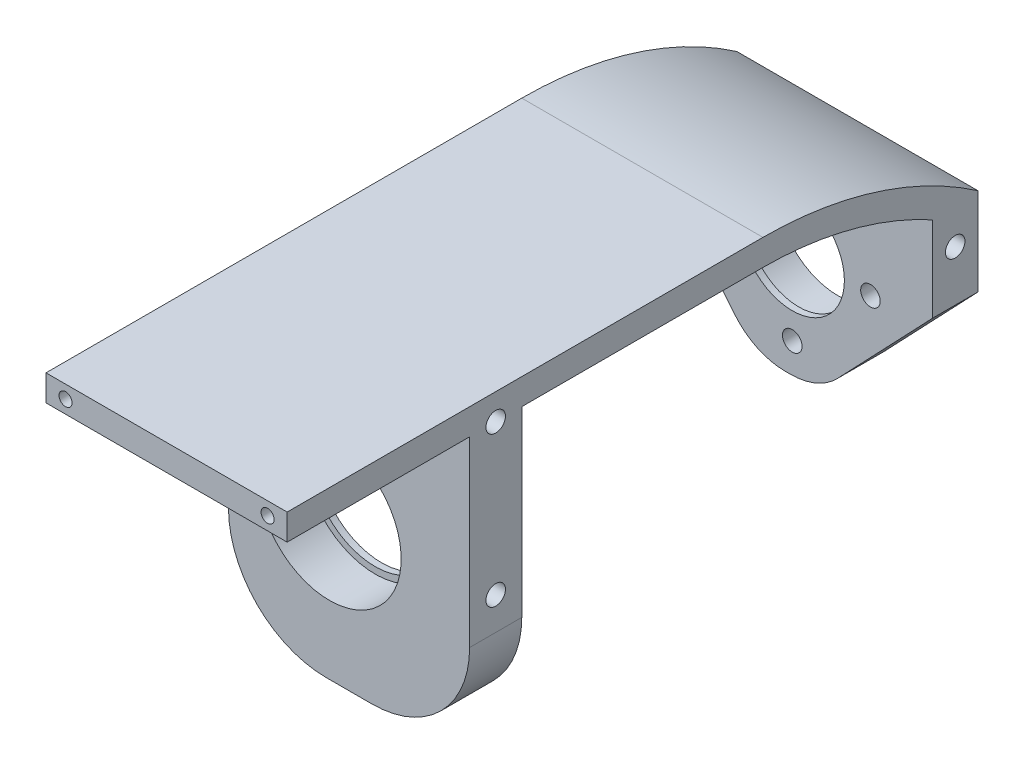
SolidWorks part; units mm, degrees
ref_plane "Front Plane" through (0, 0, 0) normal (0, 0, 1) x (1, 0, 0)
ref_plane "Top Plane" through (0, 0, 0) normal (0, 1, 0) x (1, 0, 0)
ref_plane "Right Plane" through (0, 0, 0) normal (1, 0, 0) x (0, 0, -1)
sketch "Sketch3" plane through (0, 0, 0) normal (1, 0, 0) x (0, 0, -1)
  line L0 (0, 0) -> (73, 0)
  line L1 (0, 0) -> (0, -4)
  line L2 (0, -4) -> (73, -4)
  line L4 (113.6909, -22.5) -> (70.143, -22.5) construction
  line L6 (90.9961, -30.5) -> (104.9961, -30.5) construction
  line L7 (90.9961, -30.5) -> (90.9961, -14.5) construction
  line L8 (90.9961, -14.5) -> (104.9961, -14.5) construction
  line L9 (104.9961, -30.5) -> (104.9961, -14.5) construction
  line L10 (90.9961, -30.5) -> (104.9961, -14.5) construction
  line L11 (90.9961, -14.5) -> (104.9961, -30.5) construction
  line L13 (109.8205, -18.5) -> (115.4706, -18.5)
  arc A0 (73, 0) -> (115.4706, -18.5) centre (73, -58) cw
  arc A1 (73, -4) -> (104.9961, -14.5) centre (73, -58) cw
  arc A2 (104.9961, -14.5) -> (109.8205, -18.5) centre (73, -58) cw
  point P9 (97.9961, -22.5)
  dimension "D1" = 58
  dimension "D2" = 4
  dimension "D3" = 73
  dimension "D4" = 22.5
  dimension "D5" = 16
  dimension "D6" = 4
  dimension "D7" = 14
extrude "Boss-Extrude1" add sketch "Sketch3" along normal blind 37
ref_plane "Plane1" through (21.5, 0, 0) normal (1, 0, 0) x (0, 0, -1)
sketch "Sketch4" plane through (37, 0, 0) normal (1, 0, 0) x (0, 0, -1)
  line L0 (28, -4) -> (28, -14.5)
  line L1 (0, -4) -> (73, -4) construction
  line L2 (114.75, -23.7518) -> (114.75, -33.7153) construction
  line L3 (0, 0) -> (0, -4) construction
  line L4 (28, -4) -> (36, -4)
  line L5 (36, -4) -> (36, -15.5)
  line L6 (36, -15.5) -> (35, -15.5) construction
  line L7 (35, -15.5) -> (35, -14.5) construction
  line L8 (35, -14.5) -> (28, -14.5) construction
  line L9 (35, -15.5) -> (35, -25.5) construction
  line L10 (35, -25.5) -> (17.1507, -25.5) construction
  line L11 (28, -14.5) -> (28, -36.5)
  line L12 (36, -15.5) -> (36, -35.5)
  line L13 (28, -47) -> (36, -47)
  line L14 (28, -47) -> (28, -36.5)
  line L15 (36, -47) -> (36, -35.5)
  line L16 (73, 0) -> (0, 0) construction
  arc A0 (109.8205, -18.5) -> (73, -4) centre (73, -58) ccw construction
  point P22 (28, -25.5)
  point P23 (36, -25.5)
  dimension "D1" = 28
  dimension "D2" = 114.75
  dimension "D3" = 25.5
  dimension "D4" = 8
  dimension "D5" = 7
  dimension "D6" = 11.5
  dimension "D7" = 11
extrude "Boss-Extrude3" add sketch "Sketch4" against normal up to surface (37 mm away) contours L11 L14 L13 L15 L12 L5 L4 L0 up to face at (0, -6.1802, -62.4324)
sketch "Sketch5" plane through (0, 0, -28) normal (0, 0, 1) x (1, 0, 0)
  line L0 (37, -25.5) -> (21.5, -25.5) construction
  line L1 (37, -47) -> (37, -4) construction
  circle A0 centre (21.5, -25.5) radius 11
  dimension "D2" = 22
  dimension "D1" = 15.5
  dimension "D3" = 21.5
extrude "Cut-Extrude1" cut sketch "Sketch5" against normal blind 7
sketch "Sketch6" plane through (0, 0, -35) normal (0, 0, 1) x (1, 0, 0)
  circle A0 centre (21.5, -25.5) radius 10
  dimension "D1" = 20
extrude "Cut-Extrude2" cut sketch "Sketch6" against normal blind 7
sketch "Sketch7" plane through (37, 0, 0) normal (1, 0, 0) x (0, 0, -1)
  line L0 (36, -4) -> (99, -4) construction
  line L1 (99, -4) -> (99, -10.6714) construction
  line L2 (67.5, -4) -> (67.5, -25.5) construction
  line L3 (67.5, -25.5) -> (116.1248, -25.5) construction
  line L4 (99, -10.6714) -> (99, -16) construction
  line L5 (99, -16) -> (105, -16) construction
  line L6 (105, -16) -> (105, -17.5) construction
  line L7 (105, -17.5) -> (106, -17.5) construction
  line L8 (106, -17.5) -> (106, -15.2566) construction
  line L9 (99, -10.6714) -> (99, -47)
  line L10 (99, -47) -> (106, -47)
  line L11 (106, -47) -> (106, -15.2566)
  arc A0 (109.8205, -18.5) -> (73, -4) centre (73, -58) ccw construction
  arc A2 (106, -15.2566) -> (99, -10.6714) centre (73, -58) ccw
  dimension "D1" = 63
  dimension "D2" = 21.5
  dimension "D3" = 9.5
  dimension "D4" = 8
  dimension "D5" = 6
  dimension "D6" = 1
  dimension "D7" = 43
extrude "Boss-Extrude4" add sketch "Sketch7" against normal up to surface (37 mm away) contours L11 A2 L9 L10 up to face at (0, -13.9081, -50.2594)
sketch "Sketch8" plane through (0, 0, -106) normal (0, 0, 1) x (1, 0, 0)
  circle A0 centre (21.5, -25.5) radius 9.5
  dimension "D1" = 19
extrude "Cut-Extrude3" cut sketch "Sketch8" along normal blind 6
sketch "Sketch9" plane through (0, 0, -100) normal (0, 0, -1) x (-1, 0, 0)
  circle A0 centre (-21.5, -25.5) radius 8
  dimension "D1" = 16
extrude "Cut-Extrude4" cut sketch "Sketch9" against normal blind 1
sketch "Sketch10" plane through (0, 0, -106) normal (0, 0, -1) x (-1, 0, 0)
  line L0 (0, -23.7577) -> (-17.4711, -42.0819)
  line L1 (0, -47) -> (0, -15.2566) construction
  line L2 (-17.4711, -42.0819) -> (-27.3185, -42.0819)
  line L3 (-27.3185, -42.0819) -> (-37, -30.2284)
  line L4 (-37, -47) -> (-37, -15.2566) construction
  line L5 (-37, -30.2284) -> (-37, -47)
  line L6 (-37, -47) -> (0, -47)
  line L7 (0, -47) -> (0, -23.7577)
extrude "Cut-Extrude5" cut sketch "Sketch10" against normal up to surface (7 mm away) up to face at (13.5, -25.5, -99)
sketch "Sketch11" plane through (37, 0, 0) normal (1, 0, 0) x (0, 0, -1)
  line L0 (106, -15.2566) -> (106, -10.303)
  line L1 (109.8205, -18.5) -> (115.4706, -18.5) construction
  line L2 (109.8205, -18.5) -> (115.4706, -18.5)
  arc A0 (115.4706, -18.5) -> (73, 0) centre (73, -58) ccw construction
  arc A1 (109.8205, -18.5) -> (106, -15.2566) centre (73, -58) ccw construction
  arc A2 (109.8205, -18.5) -> (106, -15.2566) centre (73, -58) ccw
  arc A3 (115.4706, -18.5) -> (106, -10.303) centre (73, -58) ccw
extrude "Cut-Extrude6" cut sketch "Sketch11" against normal through all
fillet "Fillet2" radius 10 2 edges at (17.4711, -42.0819, -102.5) (27.3185, -42.0819, -102.5)
sketch "Sketch12" plane through (0, 0, -99) normal (0, 0, 1) x (1, 0, 0)
  line L0 (21.5, -25.5) -> (21.5, -13.5) construction
  circle A0 centre (21.5, -13.5) radius 1.5
  circle A1 centre (33.5, -25.5) radius 1.5
  circle A2 centre (21.5, -37.5) radius 1.5
  circle A3 centre (9.5, -25.5) radius 1.5
  point P12 (21.5, -25.5)
  dimension "D1" = 3
  dimension "D3" = 12
  dimension "D4" = 12
  dimension "D5" = 12
  dimension "D2" = 4
extrude "Cut-Extrude7" cut sketch "Sketch12" against normal through all
sketch "Sketch13" [suppressed] plane through (0, 0, -28) normal (0, 0, 1) x (1, 0, 0)
  line L0 (23, 0) -> (23, -32) construction
  line L1 (37, 0) -> (0, 0) construction
  line L3 (0, -47) -> (0, -4) construction
  circle A0 centre (23, -32) radius 11
  dimension "D2" = 22
  dimension "D1" = 32
  dimension "D3" = 23
extrude "Cut-Extrude8" [suppressed] cut sketch "Sketch13" against normal blind 7 contours A0
sketch "Sketch14" [suppressed] plane through (0, 0, -35) normal (0, 0, 1) x (1, 0, 0)
  circle A0 centre (23, -32) radius 10
  dimension "D1" = 20
extrude "Cut-Extrude9" [suppressed] cut sketch "Sketch14" against normal blind 7
sketch "Sketch15" [suppressed] plane through (0, 0, 0) normal (-1, 0, 0) x (0, 0, 1)
  line L0 (-94, -8.2506) -> (-94, -47)
  line L1 (-94, -47) -> (-101, -47)
  line L2 (-101, -47) -> (-101, -11.8264)
  line L3 (-36, -4) -> (-36, -47) construction
  line L4 (-28, -47) -> (-36, -47) construction
  arc A0 (-73, -4) -> (-109.8205, -18.5) centre (-73, -58) ccw construction
  arc A1 (-94, -8.2506) -> (-101, -11.8264) centre (-73, -58) ccw
  dimension "D1" = 58
  dimension "D2" = 7
extrude "Boss-Extrude5" [suppressed] add sketch "Sketch15" against normal up to surface (37 mm away) up to face at (37, -15.6062, -57.1006)
sketch "Sketch16" [suppressed] plane through (0, 0, -94) normal (0, 0, 1) x (1, 0, 0)
  circle A0 centre (23, -32) radius 8
  dimension "D1" = 16
extrude "Cut-Extrude10" [suppressed] cut sketch "Sketch16" against normal blind 1
sketch "Sketch17" [suppressed] plane through (0, 0, -95) normal (0, 0, 1) x (1, 0, 0)
  circle A0 centre (23, -32) radius 9.5
  dimension "D1" = 19
extrude "Cut-Extrude11" [suppressed] cut sketch "Sketch17" against normal through all
sketch "Sketch18" [suppressed] plane through (37, 0, 0) normal (1, 0, 0) x (0, 0, -1)
  line L0 (101, -11.8264) -> (101, -7.2063)
  line L1 (109.8205, -18.5) -> (115.4706, -18.5) construction
  line L2 (109.8205, -18.5) -> (115.4706, -18.5)
  arc A0 (115.4706, -18.5) -> (73, 0) centre (73, -58) ccw construction
  arc A1 (109.8205, -18.5) -> (101, -11.8264) centre (73, -58) ccw construction
  arc A2 (115.4706, -18.5) -> (101, -7.2063) centre (73, -58) ccw
  arc A3 (109.8205, -18.5) -> (101, -11.8264) centre (73, -58) ccw
extrude "Cut-Extrude12" [suppressed] cut sketch "Sketch18" against normal through all
sketch "Sketch19" [suppressed] plane through (0, 0, -101) normal (0, 0, -1) x (-1, 0, 0)
  line L0 (-23, -32) -> (-23, -20) construction
  circle A0 centre (-23, -20) radius 1.5
  circle A1 centre (-11, -32) radius 1.5
  circle A2 centre (-23, -44) radius 1.5
  circle A3 centre (-35, -32) radius 1.5
  point P12 (-23, -32)
  dimension "D1" = 3
  dimension "D2" = 12
  dimension "D4" = 12
  dimension "D5" = 12
  dimension "D3" = 4
extrude "Cut-Extrude13" [suppressed] cut sketch "Sketch19" against normal up to surface (7 mm away)
fillet "Fillet3" [suppressed] radius 10
fillet "Fillet4" [suppressed] radius 10
fillet "Fillet5" radius 15 2 edges at (0, -47, -32) (37, -47, -32)
sketch "Sketch20" plane through (0, 0, 0) normal (-1, 0, 0) x (0, 0, 1)
  line L0 (-28, -4) -> (-36, -4) construction
  line L1 (-99, -10.6714) -> (-106, -10.6714) construction
  line L2 (-106, -23.7577) -> (-106, -10.303) construction
  line L3 (-102.5, -10.6714) -> (-102.5, -16) construction
  line L4 (-73, 0) -> (0, 0) construction
  line L5 (-32, -4) -> (-32, 0) construction
  line L6 (-32, -32) -> (-32, -27) construction
  line L7 (-36, -32) -> (-28, -32) construction
  line L8 (0, 0) -> (0, -4) construction
  circle A0 centre (-32, -4) radius 1.5
  circle A1 centre (-102.5, -16) radius 1.5
  circle A2 centre (-32, -27) radius 1.5
  dimension "D1" = 3
  dimension "D2" = 3
  dimension "D5" = 3
  dimension "D3" = 16
  dimension "D4" = 5
  dimension "D6" = 23
  dimension "D7" = 32
  dimension "D8" = 102.5
extrude "Cut-Extrude14" cut sketch "Sketch20" against normal blind 6
sketch "Sketch21" plane through (0, 0, 0) normal (0, 0, 1) x (1, 0, 0)
  line L0 (0, 0) -> (0, -4) construction
  line L1 (0, -2) -> (3, -2) construction
  line L2 (37, -2) -> (34, -2) construction
  line L3 (37, 0) -> (37, -4) construction
  circle A0 centre (3, -2) radius 1
  circle A1 centre (34, -2) radius 1
  dimension "D2" = 2
  dimension "D4" = 2
  dimension "D1" = 3
  dimension "D3" = 3
  dimension "D5" = 31
extrude "Cut-Extrude15" cut sketch "Sketch21" against normal blind 6 contours A0 | A1
sketch "Sketch22" [suppressed] plane through (0, 0, 0) normal (-1, 0, 0) x (0, 0, 1)
  line L0 (-94, -8.2506) -> (-101, -8.2506) construction
  line L1 (-101, -7.2063) -> (-101, -37) construction
  line L2 (-36, -4) -> (-28, -4) construction
  line L3 (-73, 0) -> (0, 0) construction
  circle A0 centre (-97.5, -16) radius 1.5
  circle A1 centre (-32, -4) radius 1.5
  circle A2 centre (-32, -27) radius 1.5
  point P7 (-97.5, -8.2506)
  dimension "D2" = 3
  dimension "D3" = 3
  dimension "D5" = 3
  dimension "D1" = 16
  dimension "D4" = 23
extrude "Cut-Extrude16" [suppressed] cut sketch "Sketch22" against normal blind 6
mirror "Mirror1" about plane through (37, -58, -73) normal (-1, 0, 0) of bodies 121
delete or keep bodies "Body-Delete/Keep 1" type delete bodies bodies 121
mirror "Mirror2" [suppressed] of bodies 122
delete or keep bodies "Body-Delete/Keep 2" [suppressed] type delete bodies bodies 122
equation "\"mini-flipper-shaft-diameter\"= 26mm"
equation "\"mini-shaft-ring-groove-diam\"= 7.8mm"
equation "\"mini-shaft-ring-groove-width\"= 1mm"
equation "\"dtCoverPlate-DistFrom-GearCent\"= 73mm"
equation "\"wormGearShaft-L\"= \"dtCoverPlate-DistFrom-GearCent\" - 27.75 + 3.75"
equation "\"wormGearShaft-Dsmall\"= 6mm"
equation "\"wormGearShaft-Dworm\"= 12mm"
equation "\"wormL-D\" = 12mm"
equation "\"wormR-D\" = 15mm"
equation "\"wormGearL-D\" = 40mm"
equation "\"wormGearR-D\" = 50mm"
